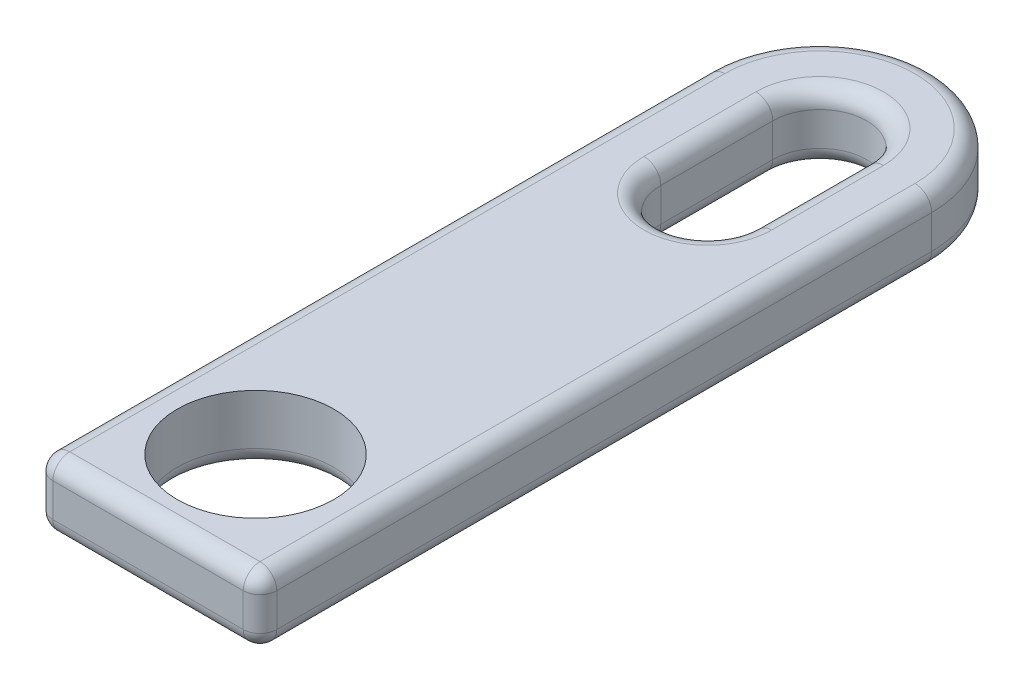
SolidWorks part; units mm, degrees
ref_plane "Front Plane" through (0, 0, 0) normal (0, 0, 1) x (1, 0, 0)
ref_plane "Top Plane" through (0, 0, 0) normal (0, 1, 0) x (1, 0, 0)
ref_plane "Right Plane" through (0, 0, 0) normal (1, 0, 0) x (0, 0, -1)
sketch "Sketch1" plane through (0, 0, 0) normal (0, 1, 0) x (1, 0, 0)
  line L0 (0, -7.4492) -> (0, -12.4492) construction
  line L6 (-5, -37.4492) -> (5, -37.4492)
  line L8 (2.1, -7.4492) -> (2.1, -12.4492)
  line L9 (-2.1, -7.4492) -> (-2.1, -12.4492)
  line L10 (-5, -7.4492) -> (5, -7.4492) construction
  line L11 (5, -7.4492) -> (5, -37.4492)
  line L12 (-5, -7.4492) -> (-5, -37.4492)
  line L13 (-5, -32.6492) -> (5, -32.6492) construction
  line L14 (0, -2.4492) -> (0, -37.4492) construction
  arc A4 (2.1, -7.4492) -> (-2.1, -7.4492) centre (0, -7.4492) ccw
  circle A5 centre (0, -32.6492) radius 3.5
  arc A6 (-2.1, -12.4492) -> (2.1, -12.4492) centre (0, -12.4492) ccw
  arc A7 (-5, -7.4492) -> (5, -7.4492) centre (0, -7.4492) cw
  point P3 (0, -9.9492)
  point P15 (0, -32.6492)
  point P17 (0, -7.4492)
  dimension "D5" = 4.8
  dimension "D2" = 2.1
  dimension "D7" = 7
  dimension "D1" = 5
  dimension "D4" = 30
  dimension "D9" = 10
extrude "Boss-Extrude1" add sketch "Sketch1" along normal blind 3
fillet "Fillet1" radius 0.75 19 edges at (0, 3, 37.4492) (2.1, 0, 9.9492) (0, 0, 14.5492) (-2.1, 0, 9.9492) (0, 0, 5.3492) (0, 0, 37.4492) (0, 3, 2.4492) (0, 0, 2.4492) (0, 3, 5.3492) (2.1, 3, 9.9492) (0, 3, 14.5492) (-2.1, 3, 9.9492) (0, 0, 36.1492) (-5, 3, 22.4492) (5, 3, 22.4492) (-5, 1.5, 37.4492) (5, 1.5, 37.4492) (-5, 0, 22.4492) (5, 0, 22.4492)
